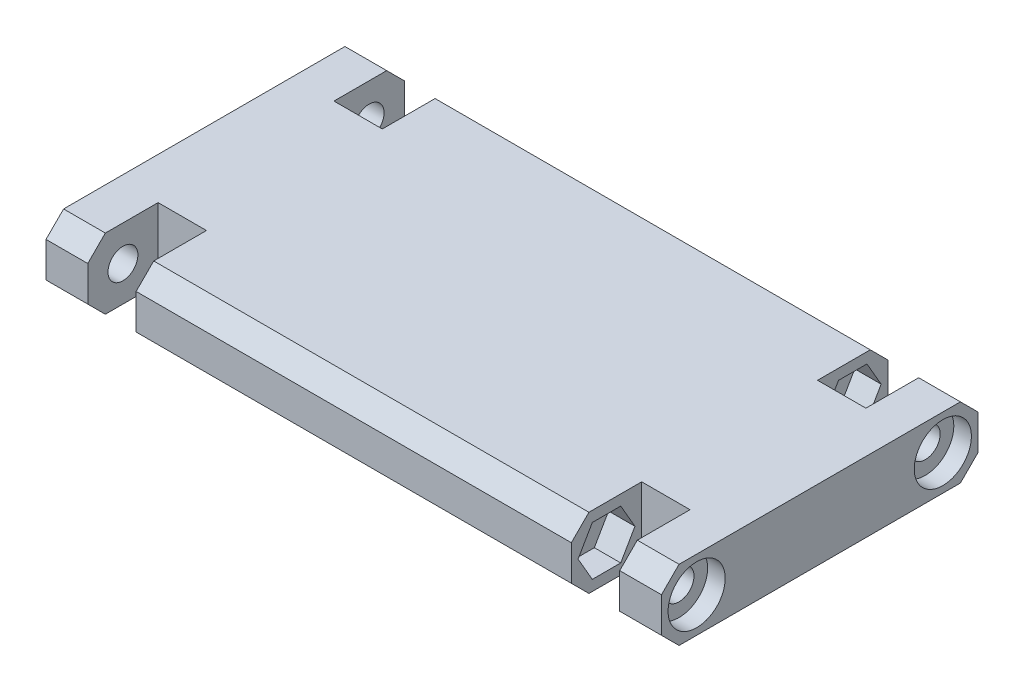
SolidWorks part; units mm, degrees
ref_plane "Front Plane" through (0, 0, 0) normal (0, 0, 1) x (1, 0, 0)
ref_plane "Top Plane" through (0, 0, 0) normal (0, 1, 0) x (1, 0, 0)
ref_plane "Right Plane" through (0, 0, 0) normal (1, 0, 0) x (0, 0, -1)
sketch "Sketch1" plane through (0, 0, 0) normal (0, 1, 0) x (1, 0, 0)
  line L1 (-35, -18) -> (35, -18)
  line L2 (-35, -18) -> (-35, 18)
  line L3 (-35, 18) -> (35, 18)
  line L4 (35, -18) -> (35, 18)
  line L5 (-35, -18) -> (35, 18) construction
  line L6 (-35, 18) -> (35, -18) construction
  point P0 (0, 0)
  dimension "D1" = 70
  dimension "D2" = 36
extrude "Boss-Extrude1" add sketch "Sketch1" along normal blind 8
sketch "Sketch2" plane through (0, 8, 0) normal (0, 1, 0) x (1, 0, 0)
  line L0 (35, 18) -> (-35, 18) construction
  line L1 (-30.25, 18) -> (-24.75, 18)
  line L2 (-30.25, 18) -> (-30.25, 10)
  line L3 (-30.25, 10) -> (-24.75, 10)
  line L4 (-24.75, 18) -> (-24.75, 10)
  line L5 (0, 0) -> (0, 18) construction
  line L6 (24.75, 18) -> (24.75, 10)
  line L7 (30.25, 10) -> (24.75, 10)
  line L8 (30.25, 18) -> (30.25, 10)
  line L9 (30.25, 18) -> (24.75, 18)
  dimension "D1" = 5.5
  dimension "D2" = 8
  dimension "D3" = 49.5
extrude "Cut-Extrude1" cut sketch "Sketch2" against normal through all
hole_wizard "CBORE for M3 Cheese Head Screw1" positions "Sketch7" profile "Sketch8" counterbore size "M3" standard "ISO" end condition up to next
sketch "Sketch7" plane through (35, 0, 0) normal (1, 0, 0) x (0, 0, -1)
  line L0 (-18, 8) -> (18, 8) construction
  line L1 (18, 8) -> (18, 0) construction
  point P0 (14, 4)
  dimension "D1" = 4
  dimension "D2" = 4
sketch "Sketch8" plane through (35, 4, -14) normal (0, 1, 0) x (0, 0, -1)
  line L0 (0, 0) -> (0, 56.75)
  line L1 (0, 56.75) -> (1.7, 56.75)
  line L3 (1.7, 56.75) -> (1.7, 2)
  line L4 (1.7, 2) -> (3.25, 2)
  line L5 (3.25, 2) -> (3.25, 0)
  line L7 (3.25, 0) -> (0, 0)
  line L11 (0, -6.35) -> (0, 107.95) construction
  dimension "Thru Hole Dia." = 3.4
  dimension "Thru Hole Depth" = 56.75
  dimension "C'Bore Dia." = 6.5
  dimension "C'Bore Depth" = 2
sketch "Sketch9" plane through (24.75, 0, 0) normal (1, 0, 0) x (0, 0, -1)
  line L1 (15.6166, 6.8) -> (12.3834, 6.8)
  line L2 (12.3834, 6.8) -> (10.7668, 4)
  line L3 (10.7668, 4) -> (12.3834, 1.2)
  line L4 (12.3834, 1.2) -> (15.6166, 1.2)
  line L5 (15.6166, 1.2) -> (17.2332, 4)
  line L6 (17.2332, 4) -> (15.6166, 6.8)
  circle A0 centre (14, 4) radius 2.8 construction
  dimension "D1" = 5.6
extrude "Cut-Extrude2" cut sketch "Sketch9" against normal blind 3
mirror "Mirror1" about plane through (0, 0, 0) normal (1, 0, 0) of "Cut-Extrude2", "CBORE for M3 Cheese Head Screw1"
mirror "Mirror2" about plane through (0, 0, 0) normal (0, 0, 1) of "Cut-Extrude1", "CBORE for M3 Cheese Head Screw1", "Cut-Extrude2", "Mirror1"
chamfer "Chamfer1" distance 2 angle 45 12 edges at (32.625, 0, -18) (32.625, 8, -18) (0, 0, -18) (0, 8, -18) (-32.625, 0, -18) (-32.625, 8, -18) (-32.625, 0, 18) (32.625, 0, 18) (0, 0, 18) (32.625, 8, 18) (-32.625, 8, 18) (0, 8, 18)
